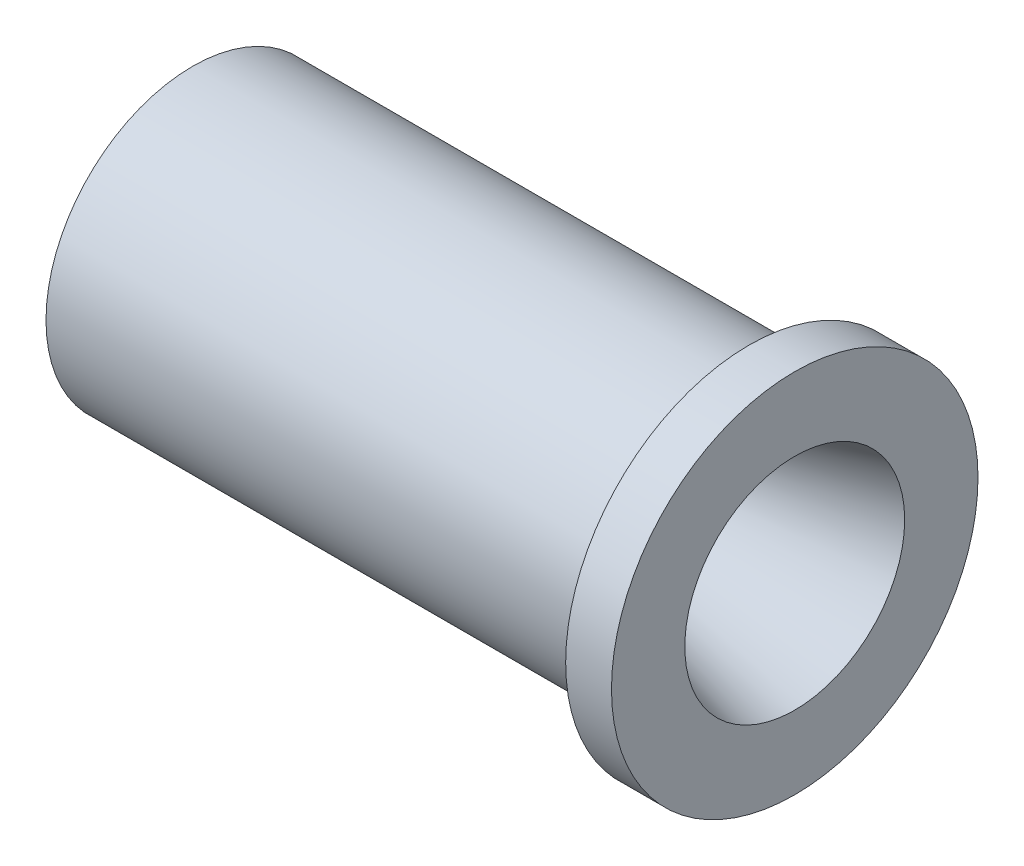
SolidWorks part; units mm, degrees
ref_plane "Front Plane" through (0, 0, 0) normal (0, 0, 1) x (1, 0, 0)
ref_plane "Top Plane" through (0, 0, 0) normal (0, 1, 0) x (1, 0, 0)
ref_plane "Right Plane" through (0, 0, 0) normal (1, 0, 0) x (0, 0, -1)
sketch "Sketch1" plane through (0, 0, 0) normal (0, 0, 1) x (1, 0, 0)
  line L0 (0, 0) -> (2773.6243, 0) construction
  line L1 (-16.7591, 5.08) -> (-6.5991, 5.08)
  line L2 (-6.5991, 5.08) -> (0, 1.27)
  line L3 (0, 1.27) -> (1.27, 1.27)
  line L4 (1.27, 1.27) -> (24.9685, 7.62)
  line L5 (24.9685, 7.62) -> (24.9685, 12.7)
  line L6 (24.9685, 12.7) -> (21.7935, 12.7)
  line L7 (21.7935, 12.7) -> (21.7935, 10.16)
  line L8 (21.7935, 10.16) -> (-16.7591, 10.16)
  line L9 (-16.7591, 10.16) -> (-16.7591, 5.08)
  line L10 (0, 0) -> (0, 50000) construction
  dimension "D1" = 1.27
  dimension "D2" = 1.27
  dimension "D3" = 5.08
  dimension "D4" = 30
  dimension "D5" = 15
  dimension "D8" = 7.62
  dimension "D9" = 10.16
  dimension "D10" = 3.175
  dimension "D6" = 10.16
  dimension "D7" = 12.7
revolve "Revolve1" add sketch "Sketch1" angle 360 about L0
equation "\"r_throat\"= 0.05"
equation "\"r_exit\"= 0.3"
equation "\"l_throat\"= 0.05"
equation "\"OD\"= 0.8"
equation "\"thread_nom_diam\"= 0.4"
equation "\"l_thread\"= 0.4"
equation "\"l_flange\"= 0.125"
equation "\"D9@Sketch1\"=\"l_thread\""
equation "\"D3@Sketch1\"=\"thread_nom_diam\"/2"
equation "\"D2@Sketch1\"=\"l_throat\""
equation "\"D1@Sketch1\"=\"r_throat\""
equation "\"D8@Sketch1\"=\"r_exit\""
equation "\"D10@Sketch1\"=\"l_flange\""
equation "\"d_flange\"= 1"
equation "\"D6@Sketch1\"=\"OD\"/2"
equation "\"D7@Sketch1\"=\"d_flange\"/2"
